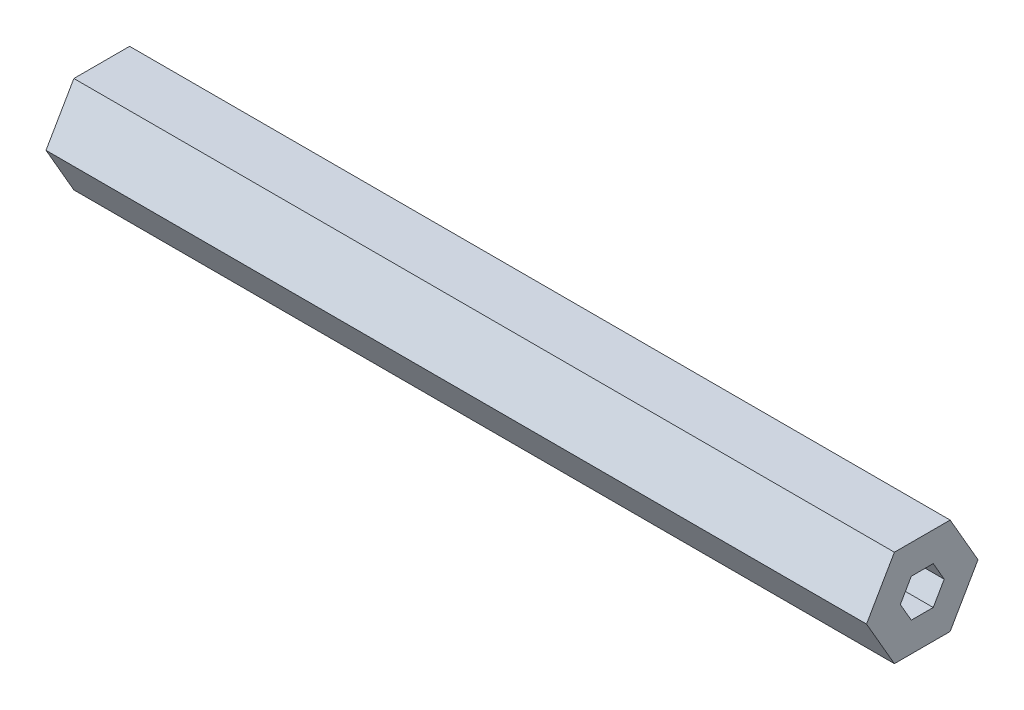
SolidWorks part; units mm, degrees
material "6061-T6 (SS)"
ref_plane "Front" through (0, 0, 0) normal (0, 0, 1) x (1, 0, 0)
ref_plane "Top" through (0, 0, 0) normal (0, 1, 0) x (1, 0, 0)
ref_plane "Right" through (0, 0, 0) normal (1, 0, 0) x (0, 0, -1)
sketch "Sketch1" plane through (0, 0, 0) normal (1, 0, 0) x (0, 0, -1)
  line L1 (7.3323, 0) -> (3.6662, 6.35)
  line L2 (3.6662, 6.35) -> (-3.6662, 6.35)
  line L3 (-3.6662, 6.35) -> (-7.3323, 0)
  line L4 (-7.3323, 0) -> (-3.6662, -6.35)
  line L5 (-3.6662, -6.35) -> (3.6662, -6.35)
  line L6 (3.6662, -6.35) -> (7.3323, 0)
  line L7 (2.8868, 0) -> (1.4434, 2.5)
  line L8 (1.4434, 2.5) -> (-1.4434, 2.5)
  line L9 (-1.4434, 2.5) -> (-2.8868, 0)
  line L10 (-2.8868, 0) -> (-1.4434, -2.5)
  line L11 (-1.4434, -2.5) -> (1.4434, -2.5)
  line L12 (1.4434, -2.5) -> (2.8868, 0)
  circle A0 centre (0, 0) radius 6.35 construction
  circle A1 centre (0, 0) radius 2.5 construction
  dimension "D1" = 12.7
  dimension "D2" = 5
extrude "Boss-Extrude1" add sketch "Sketch1" along normal blind 107.95
ref_axis "Axis1" through (-80.9, 0, 0) along (1, 0, 0)
